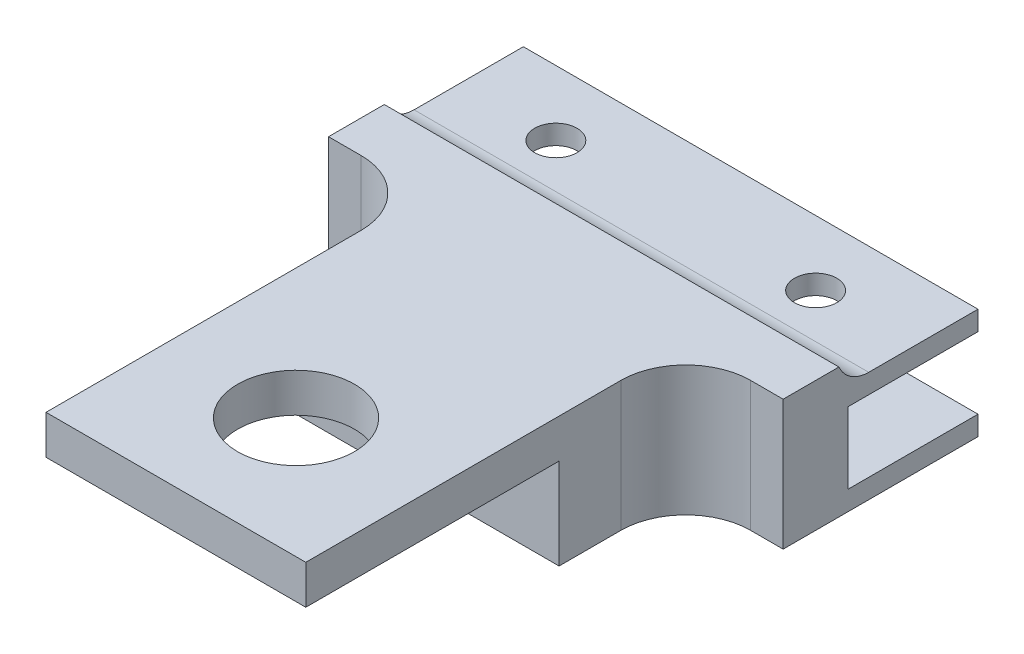
SolidWorks part; units mm, degrees
material "Pine"
ref_plane "Front Plane" through (0, 0, 0) normal (0, 0, 1) x (1, 0, 0)
ref_plane "Top Plane" through (0, 0, 0) normal (0, 1, 0) x (1, 0, 0)
ref_plane "Right Plane" through (0, 0, 0) normal (1, 0, 0) x (0, 0, -1)
sketch "Sketch1" plane through (0, 0, 0) normal (0, 0, 1) x (1, 0, 0)
  line L1 (-20, -5.5) -> (20, -5.5)
  line L2 (-20, -5.5) -> (-20, 5.5)
  line L3 (-20, 5.5) -> (20, 5.5)
  line L4 (20, -5.5) -> (20, 5.5)
  line L5 (-20, -5.5) -> (20, 5.5) construction
  line L6 (-20, 5.5) -> (20, -5.5) construction
  point P0 (0, 0)
  dimension "D1" = 40
  dimension "D2" = 11
extrude "Boss-Extrude1" add sketch "Sketch1" along normal blind 19.5
sketch "Sketch2" plane through (0, 0, 0) normal (0, 0, -1) x (-1, 0, 0)
  line L1 (-35, -5.5) -> (35, -5.5)
  line L2 (-35, -5.5) -> (-35, 5.5)
  line L3 (-35, 5.5) -> (35, 5.5)
  line L4 (35, -5.5) -> (35, 5.5)
  line L5 (-35, -5.5) -> (35, 5.5) construction
  line L6 (-35, 5.5) -> (35, -5.5) construction
  point P0 (0, 0)
  dimension "D1" = 11
  dimension "D2" = 70
extrude "Boss-Extrude2" add sketch "Sketch2" along normal blind 10
sketch "Sketch3" plane through (0, 5.5, 0) normal (0, 1, 0) x (1, 0, 0)
  line L0 (-35, 10) -> (35, 10) construction
  line L1 (-35, 0) -> (35, 0)
  line L2 (-35, 0) -> (-35, 30)
  line L3 (-35, 30) -> (35, 30)
  line L4 (35, 0) -> (35, 30)
  line L5 (-35, 0) -> (35, 30) construction
  line L6 (-35, 30) -> (35, 0) construction
  line L8 (-20, 0) -> (20, 0)
  line L9 (-20, 0) -> (-20, -19.5)
  line L10 (-20, -19.5) -> (20, -19.5)
  line L11 (20, 0) -> (20, -19.5)
  point P0 (0, 15)
  line M6 (20, -19.5) -> (20, 0)
  line M7 (20, 0) -> (35, 0)
  line M8 (35, 0) -> (35, 10)
  line M9 (35, 10) -> (-35, 10)
  line M10 (-35, 10) -> (-35, 0)
  line M11 (-35, 0) -> (-20, 0)
  line M12 (-20, 0) -> (-20, -19.5)
  line M13 (-20, -19.5) -> (20, -19.5)
  dimension "D1" = 70
  dimension "D2" = 30
  dimension "D3" = 10
  dimension "D4" = 20
extrude "Boss-Extrude4" add sketch "Sketch3" along normal blind 3 contours L4 L3 L2 M9 | L1 M11 M7 M8 M9 M10 | L1 M12 M13 M6
sketch "Sketch4" plane through (0, -5.5, 0) normal (0, -1, 0) x (1, 0, 0)
  line L1 (-35, -30) -> (35, -30)
  line L2 (-35, -30) -> (-35, 0)
  line L3 (-35, 0) -> (35, 0)
  line L4 (35, -30) -> (35, 0)
  line L5 (-20, 19.5) -> (20, 19.5)
  line L6 (-20, 19.5) -> (-20, 0)
  line L7 (-20, 0) -> (20, 0)
  line L8 (20, 19.5) -> (20, 0)
  line M1 (-20, 19.5) -> (-20, 0)
  line M4 (-35, -10) -> (35, -10)
  line M7 (20, 0) -> (20, 19.5)
  line M8 (20, 19.5) -> (-20, 19.5)
extrude "Boss-Extrude5" add sketch "Sketch4" along normal blind 3 contours L1 L4 L2 M4 | L3 M1 M7 M8
sketch "Sketch5" plane through (0, -8.5, 0) normal (0, -1, 0) x (1, 0, 0)
  line L0 (-35, -30) -> (-35, 0) construction
  line L1 (-35, -30) -> (35, -30) construction
  line L2 (0, -30) -> (0, -25.2737) construction
  circle A0 centre (-20, -20) radius 3.2645
  circle A1 centre (20, -20) radius 3.2645
  dimension "D1" = 6.529
  dimension "D2" = 15
  dimension "D3" = 10
extrude "Cut-Extrude1" cut sketch "Sketch5" against normal through all
sketch "Sketch6" plane through (0, 8.5, 0) normal (0, 1, 0) x (1, 0, 0)
  line L0 (-35, 0) -> (-35, 30) construction
  line L1 (20, -19.5) -> (-20, -19.5)
  line L2 (20, -19.5) -> (20, -58.5)
  line L3 (20, -58.5) -> (-20, -58.5)
  line L4 (-20, -19.5) -> (-20, -58.5)
  line L5 (20, -19.5) -> (-20, -19.5)
  line L6 (20, -19.5) -> (20, 0)
  line L7 (20, 0) -> (-20, 0)
  line L8 (-20, -19.5) -> (-20, 0)
  line L9 (35, 0) -> (-35, 0)
  line L10 (35, 0) -> (35, 8.5881)
  line L11 (35, 8.5881) -> (-35, 8.5881)
  line L12 (-35, 0) -> (-35, 8.5881)
  circle A0 centre (0, -40) radius 9
  line M8 (-35, 30) -> (-35, 0)
  line M9 (-35, 0) -> (-20, 0)
  line M10 (-20, 0) -> (-20, -19.5)
  line M11 (-20, -19.5) -> (20, -19.5)
  line M12 (20, -19.5) -> (20, 0)
  line M13 (20, 0) -> (35, 0)
  line M14 (35, 0) -> (35, 30)
  dimension "D3" = 18
  dimension "D4" = 20.5
  dimension "D5" = 20
  dimension "D1" = 40
  dimension "D2" = 39
extrude "Boss-Extrude6" add sketch "Sketch6" along normal blind 3 and the other way blind 3 contours L11 L7 M14 M8 M9 M13 | L7 M12 M10 M11 | L4 L3 L2 A0 M11
fillet "Fillet1" radius 5 1 edges at (0, 8.5, -8.5881)
fillet "Fillet2" radius 10 2 edges at (20, 1.5, 0) (-20, 1.5, 0)
